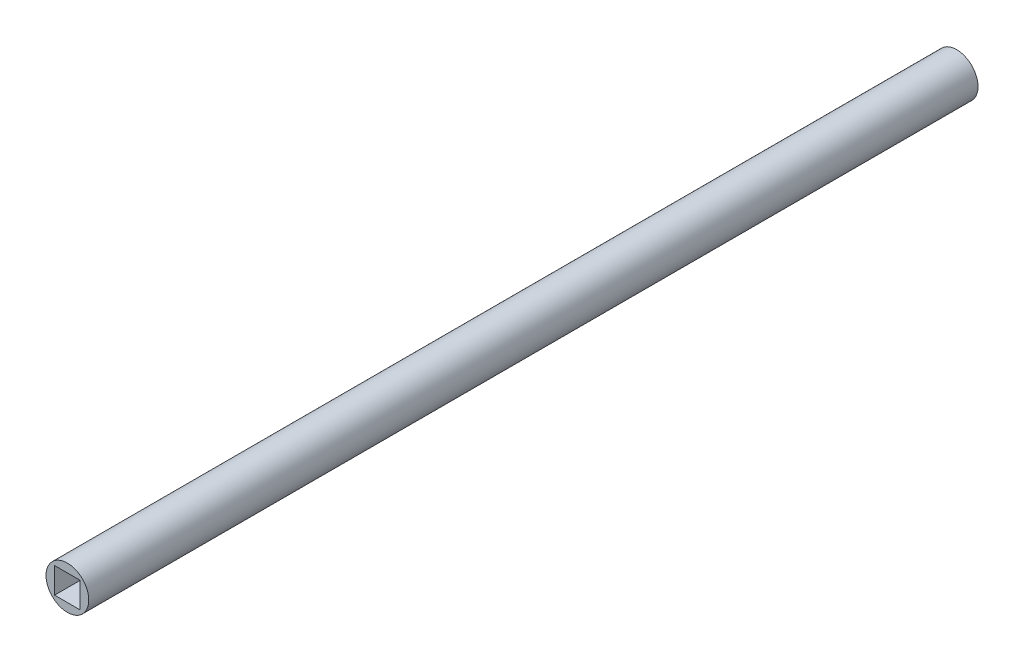
SolidWorks part; units mm, degrees
material "PLA"
ref_plane "Front Plane" through (0, 0, 0) normal (0, 0, 1) x (1, 0, 0)
ref_plane "Top Plane" through (0, 0, 0) normal (0, 1, 0) x (1, 0, 0)
ref_plane "Right Plane" through (0, 0, 0) normal (1, 0, 0) x (0, 0, -1)
sketch "Sketch1" plane through (0, 0, 0) normal (0, 1, 0) x (1, 0, 0)
  line L1 (0, 0) -> (-15.875, 0)
  line L2 (0, 0) -> (0, -660.4)
  line L3 (0, -660.4) -> (-15.875, -660.4)
  line L4 (-15.875, 0) -> (-15.875, -660.4)
  dimension "D1" = 660.4
  dimension "D2" = 15.875
revolve "Revolve1" add sketch "Sketch1" angle 360 about L2
sketch "Sketch2" plane through (0, 0, 660.4) normal (0, 0, 1) x (1, 0, 0)
  line L1 (-9.525, 9.525) -> (9.525, 9.525)
  line L2 (-9.525, 9.525) -> (-9.525, -9.525)
  line L3 (-9.525, -9.525) -> (9.525, -9.525)
  line L4 (9.525, 9.525) -> (9.525, -9.525)
  line L5 (-9.525, 9.525) -> (9.525, -9.525) construction
  line L6 (-9.525, -9.525) -> (9.525, 9.525) construction
  point P0 (0, 0)
  dimension "D1" = 19.05
  dimension "D2" = 19.05
extrude "Cut-Extrude1" cut sketch "Sketch2" against normal through all contours L2 L1 L4 L3
